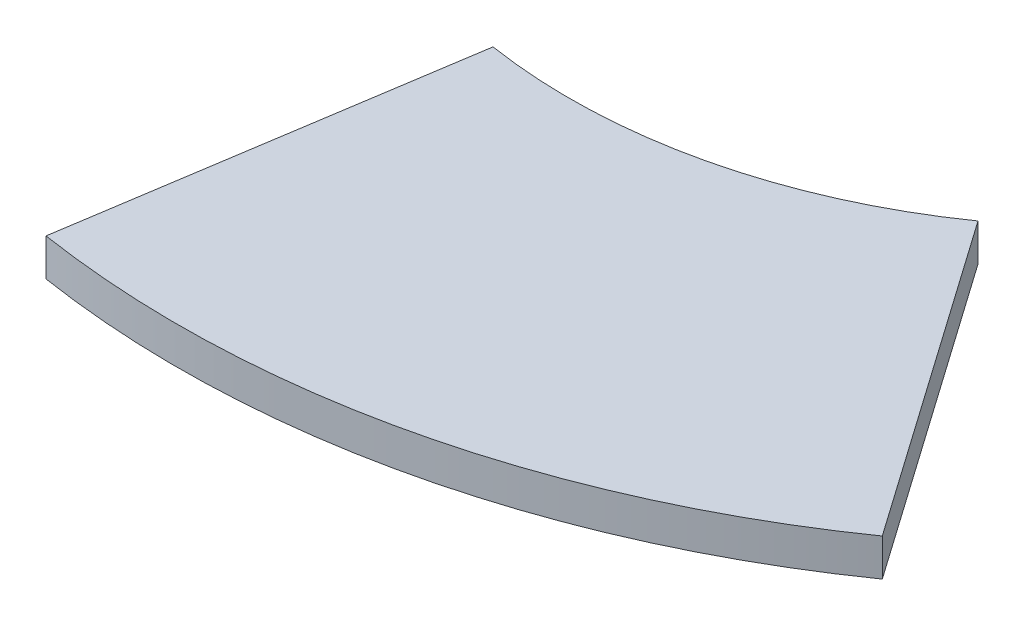
SolidWorks part; units mm, degrees
ref_plane "Front Plane" through (0, 0, 0) normal (0, 0, 1) x (1, 0, 0)
ref_plane "Top Plane" through (0, 0, 0) normal (0, 1, 0) x (1, 0, 0)
ref_plane "Right Plane" through (0, 0, 0) normal (1, 0, 0) x (0, 0, -1)
sketch "Sketch1" plane through (0, 0, 0) normal (0, 1, 0) x (1, 0, 0)
  line L0 (-15.2631, -98.8283) -> (-8.8526, -57.3204)
  line L1 (57.4299, -81.8646) -> (33.3093, -47.4814)
  arc A0 (-15.2631, -98.8283) -> (57.4299, -81.8646) centre (0, 0) ccw
  arc A1 (-8.8526, -57.3204) -> (33.3093, -47.4814) centre (0, 0) ccw
  point P6 (47.3851, -33.4463)
  point P7 (0, 0)
  point P8 (33.3093, -47.4814)
  dimension "D1" = 100
  dimension "D3" = 58
  dimension "D2" = 43.83
  dimension "D4" = 42
extrude "Boss-Extrude1" add sketch "Sketch1" along normal blind 4
